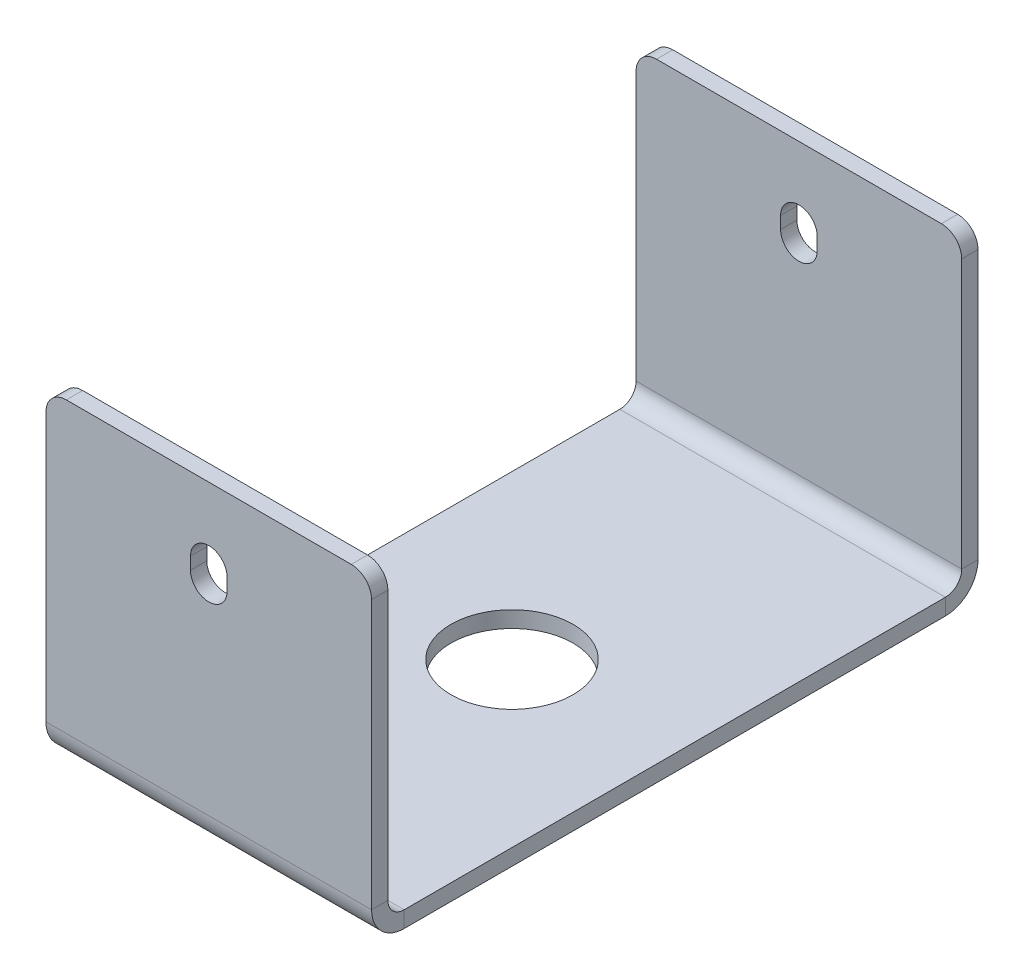
SolidWorks part; units mm, degrees
note: The reader was unsure of these and kept them because the rebuilt part matched: bend radius of "基体折弯1", "基体折弯2".
material "Q355"
ref_plane "前视基准面" through (0, 0, 0) normal (0, 0, 1) x (1, 0, 0)
ref_plane "上视基准面" through (0, 0, 0) normal (0, 1, 0) x (1, 0, 0)
ref_plane "右视基准面" through (0, 0, 0) normal (1, 0, 0) x (0, 0, -1)
sketch "草图1" plane through (0, 0, 0) normal (1, 0, 0) x (0, 0, -1)
  line L0 (-70.5, 75) -> (-70.5, 0)
  line L1 (-70.5, 0) -> (70.5, 0)
  line L2 (70.5, 0) -> (70.5, 75)
  dimension "D1" = 141
  dimension "D2" = 75
base flange "基体-法兰1" sketch "草图1" end condition mid plane depth 80 reverse direction no thickness 4 reverse thickness direction no bend radius 4
bend "基体折弯1" bend radius 4 bend angle 90 parameters "D5"=1
bend "基体折弯2" bend radius 4 bend angle 90 parameters "D5"=2
sketch "草图6" plane through (0, -4, 0) normal (0, -1, 0) x (1, 0, 0)
  circle A0 centre (0, 0) radius 15
  dimension "D1" = 30
extrude "切除-拉伸1" cut sketch "草图6" against normal up to next
sketch "草图7" plane through (0, 0, 74.5) normal (0, 0, 1) x (1, 0, 0)
  line L0 (0, 57) -> (0, 54) construction
  line L1 (4.5, 57) -> (4.5, 54)
  line L2 (-4.5, 57) -> (-4.5, 54)
  line L3 (40, -4) -> (-40, -4) construction
  arc A0 (4.5, 57) -> (-4.5, 57) centre (0, 57) ccw
  arc A1 (-4.5, 54) -> (4.5, 54) centre (0, 54) ccw
  point P3 (0, 55.5)
  dimension "D2" = 4.5
  dimension "D3" = 58
  dimension "D1" = 3
extrude "切除-拉伸2" cut sketch "草图7" against normal through all
fillet "圆角1" radius 5 4 edges at (-40, 75, -72.5) (40, 75, -72.5) (40, 75, 72.5) (-40, 75, 72.5)
sketch "折弯-线1" [suppressed] plane through (0, 0, 0) normal (0, 1, 0) x (1, 0, 0)
sketch "边界框1" [suppressed] plane through (0, 0, 0) normal (0, 1, 0) x (1, 0, 0)
sheet metal parameters "钣金8" thickness 4 parameters "D1"=4
flat pattern "平板型式8" [suppressed]
sketch "折弯-线2" plane through (0, 0, 0) normal (0, 1, 0) x (1, 0, 0)
sketch "边界框2" [suppressed] plane through (0, 0, 0) normal (0, 1, 0) x (1, 0, 0)
bend of the flat pattern "展开-<基体折弯1>1"
bend of the flat pattern "展开-<基体折弯2>1"
sheet metal parameters "钣金9" thickness 4 parameters "D1"=4
flat pattern "平板型式8" [suppressed]
sketch "折弯-线2" plane through (0, 0, 0) normal (0, 1, 0) x (1, 0, 0)
sketch "边界框2" [suppressed] plane through (0, 0, 0) normal (0, 1, 0) x (1, 0, 0)
bend of the flat pattern "展开-<基体折弯1>1"
bend of the flat pattern "展开-<基体折弯2>1"
sheet metal parameters "钣金10" thickness 4 parameters "D1"=4
flat pattern "平板型式8"
sketch "折弯-线2" plane through (0, 0, 0) normal (0, 1, 0) x (1, 0, 0)
  line L0 (40, -71.2124) -> (-40, -71.2124) construction
  line L1 (-40, 71.2124) -> (40, 71.2124) construction
  line L2 (40, -71.2124) -> (-40, -71.2124) construction
  line L3 (-40, 71.2124) -> (40, 71.2124) construction
sketch3d "边界框2" [suppressed]
  line L0 (0, 217.4248, 0) -> (0, -76.4248, 0) construction
  line L1 (-80, 217.4248, 0) -> (-80, -76.4248, 0) construction
  line L2 (0, 217.4248, 0) -> (-80, 217.4248, 0) construction
  line L3 (0, -76.4248, 0) -> (-80, -76.4248, 0) construction
bend of the flat pattern "展开-<基体折弯1>1"
bend of the flat pattern "展开-<基体折弯2>1"
